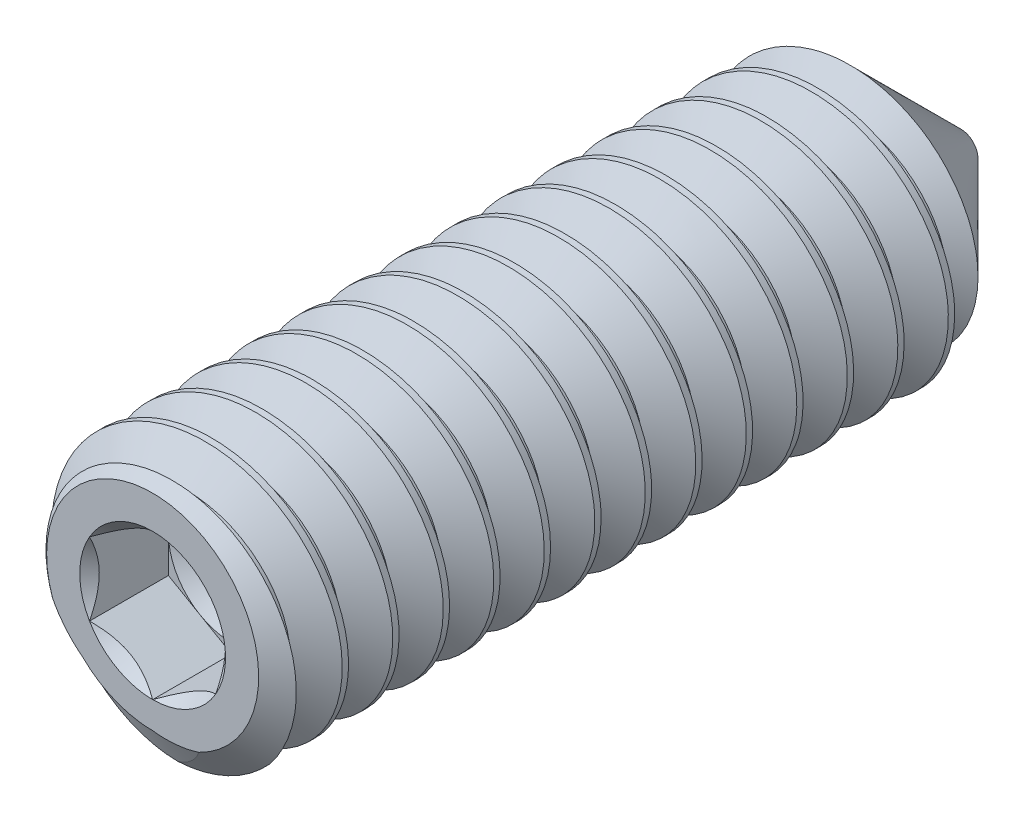
SolidWorks part; units mm, degrees
ref_plane "Front" through (0, 0, 0) normal (0, 0, 1) x (1, 0, 0)
ref_plane "Top" through (0, 0, 0) normal (0, 1, 0) x (1, 0, 0)
ref_plane "Right" through (0, 0, 0) normal (1, 0, 0) x (0, 0, -1)
sketch "Sketch22" plane through (0, 0, 0) normal (1, 0, 0) x (0, 0, -1)
  line L0 (-6.35, 0) -> (-6.35, 1.6662)
  line L1 (-6.35, 1.6662) -> (-6.0583, 2.0828)
  line L2 (-6.0583, 2.0828) -> (4.538, 2.0828)
  line L3 (4.538, 2.0828) -> (6.35, 0.2708)
  line L4 (-6.35, 1.6662) -> (-6.35, -1.6662) construction
  line L5 (6.35, 0) -> (-6.35, 0)
  line L6 (0, 2.0828) -> (0, -2.0828) construction
  line L8 (6.35, 0.2708) -> (6.35, 0)
  line L9 (-6.35, -2.0828) -> (6.35, -2.0828) construction
  line L10 (6.35, 0.2708) -> (6.35, -0.2708) construction
  line L11 (6.35, -0.2708) -> (4.538, -2.0828) construction
  line L13 (6.35, 0.2708) -> (6.0792, 0) construction
  line L15 (6.0792, 0) -> (6.35, -0.2708) construction
  dimension "D3" = 35
  dimension "D7" = 3.3325
  dimension "Dia" = 4.1656
  dimension "Length" = 12.7
  dimension "D2" = 0.5415
  dimension "D1" = 90
  dimension "D4" = 90
revolve "Revolve1" add sketch "Sketch22" angle 360 about L5
ref_plane "Plane1" through (0, 0, -6.35) normal (0, 0, 1) x (1, 0, 0)
sketch "Sketch27" plane through (0, 0, -6.35) normal (0, 0, 1) x (1, 0, 0)
  circle A0 centre (0, 0) radius 2.0828 construction
  circle A1 centre (0, 0) radius 2.0828
curve "Helix/Spiral1" pitch 0.7937 height 13.4937 radius 2.0828 centre (0, 0, -6.35) axis (0, 0, 1) start towards (0, 1, 0)
sketch "Sketch28" plane through (0, 0, 0) normal (1, 0, 0) x (0, 0, -1)
  line L0 (6.35, 2.0828) -> (7.0445, 2.0828)
  line L1 (7.0445, 2.0828) -> (6.7469, 1.5672)
  line L2 (6.7469, 1.5672) -> (6.6477, 1.5672)
  line L3 (6.6477, 1.5672) -> (6.35, 2.0828)
  line L4 (6.4988, 1.825) -> (6.8957, 1.825) construction
  line L6 (-6.0583, 2.0828) -> (4.538, 2.0828) construction
  line L7 (6.35, 1.9279) -> (6.35, -1.9279) construction
  dimension "D1" = 0.0992
  dimension "D3" = 60
  dimension "D2" = 0.3969
sweep "Cut-Sweep2" cut profiles "Sketch28" path "Helix/Spiral1" align with end faces yes
sketch "Sketch23" plane through (0, 0, 6.35) normal (0, 0, 1) x (1, 0, 0)
  line L1 (0, 1.1457) -> (-0.9922, 0.5728)
  line L2 (-0.9922, 0.5728) -> (-0.9922, -0.5728)
  line L3 (-0.9922, -0.5728) -> (0, -1.1457)
  line L4 (0, -1.1457) -> (0.9922, -0.5728)
  line L5 (0.9922, -0.5728) -> (0.9922, 0.5728)
  line L6 (0.9922, 0.5728) -> (0, 1.1457)
  circle A0 centre (0, 0) radius 0.9922 construction
  dimension "Hex" = 1.9844
extrude "Cut-Extrude10" cut sketch "Sketch23" against normal blind 1.2402
sketch "Sketch24" plane through (0, 0, 6.35) normal (0, 0, 1) x (1, 0, 0)
  circle A0 centre (0, 0) radius 1.1457
extrude "Cut-Extrude11" cut sketch "Sketch24" against normal through all draft 45
sketch "Sketch26" plane through (0, 0, 5.1098) normal (0, 0, 1) x (1, 0, 0)
  circle A0 centre (0, 0) radius 0.9922 construction
  circle A1 centre (0, 0) radius 0.9922
extrude "Cut-Extrude12" cut sketch "Sketch26" against normal through all draft 60
sketch "Sketch30" plane through (0, 0, 0) normal (1, 0, 0) x (0, 0, -1)
  line L0 (-6.0583, 2.0828) -> (4.538, 2.0828) construction
  line L1 (-6.35, 0) -> (-6.35, 1.6662) construction
  line L3 (-6.35, -2.0828) -> (6.35, -2.0828) construction
  point P0 (-6.35, 2.0828)
  point P1 (4.538, 2.0828)
  point P2 (4.538, -2.0828)
  point P11 (3.3473, -2.0828)
  dimension "D1" = 1.1906
equation "\"D7@Sketch22\"=\"Dia@Sketch22\"*.8"
equation "\"D1@Sketch28\" = \"D4@Helix/Spiral1\" * .125"
equation "\"D3@Helix/Spiral1\" = \"Length@Sketch22\" + \"D4@Helix/Spiral1\""
equation "\"D1@Sketch30\" = \"D4@Helix/Spiral1\" * 1.5"
equation "\"hex Depth@Cut-Extrude10\" = \"Hex@Sketch23\" * .625"
equation "\"D2@Sketch28\" = \"D4@Helix/Spiral1\" * .5"
equation "\"D2@Sketch22\" = \"Dia@Sketch22\" * .13"
equation "\"D4@Sketch22\" = \"D1@Sketch22\""
